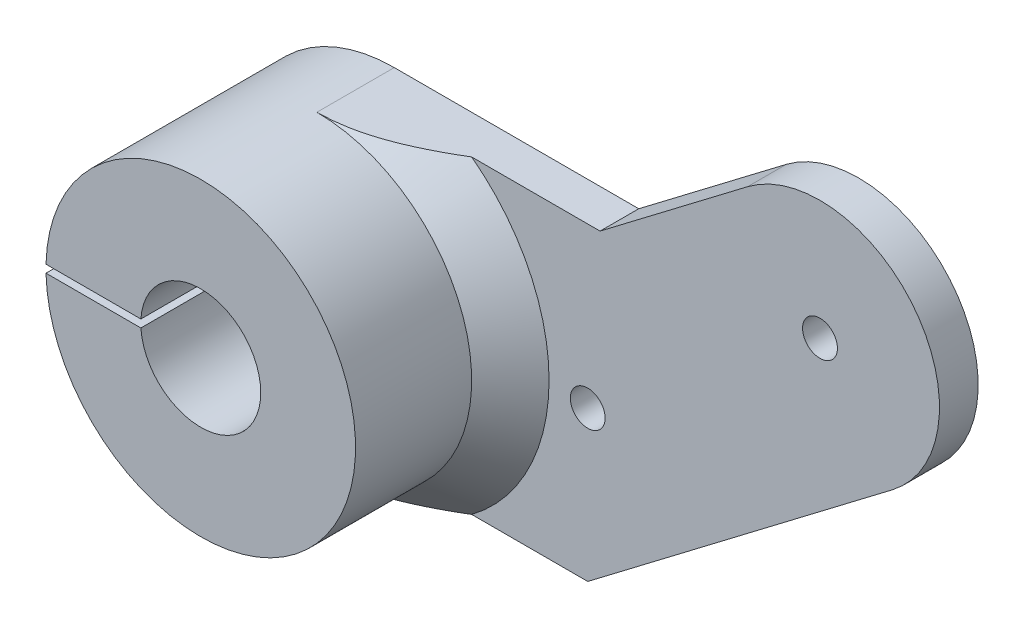
SolidWorks part; units mm, degrees
ref_plane "Front Plane" through (0, 0, 0) normal (0, 0, 1) x (1, 0, 0)
ref_plane "Top Plane" through (0, 0, 0) normal (0, 1, 0) x (1, 0, 0)
ref_plane "Right Plane" through (0, 0, 0) normal (1, 0, 0) x (0, 0, -1)
sketch "Sketch1" plane through (0, 0, 0) normal (0, 0, 1) x (1, 0, 0)
  line L0 (29.9938, -0.6088) -> (60, 22.2148) construction
  line L1 (0, 20) -> (31.5885, 20)
  line L2 (31.5885, 20) -> (50.6541, 34.5019)
  line L3 (69.3459, 9.9278) -> (30, -20)
  line L4 (30, -20) -> (0, -20)
  line L5 (-7.7339, 0.5) -> (-19.9937, 0.5)
  line L6 (-7.7339, -0.5) -> (-19.9937, -0.5)
  arc A0 (0, 20) -> (-19.9937, 0.5) centre (0, 0) ccw
  circle A1 centre (29.9938, -0.6088) radius 2.25
  circle A2 centre (60, 22.2148) radius 2.25
  arc A3 (50.6541, 34.5019) -> (69.3459, 9.9278) centre (60, 22.2148) cw
  arc A4 (-7.7339, -0.5) -> (-7.7339, 0.5) centre (0, 0) ccw
  arc A5 (-19.9937, -0.5) -> (0, -20) centre (0, 0) ccw
  circle A7 centre (60, 22.2148) radius 2 construction
  dimension "D1" = 40
  dimension "D2" = 4.5
  dimension "D5" = 15.5
  dimension "D3" = 30
  dimension "D4" = 37.7
  dimension "D6" = 0.5
  dimension "D7" = 1
extrude "Boss-Extrude1" add sketch "Sketch1" along normal blind 5
sketch "Sketch2" plane through (0, 0, 5) normal (0, 0, 1) x (1, 0, 0)
  line L6 (-7.7339, -0.5) -> (-19.9937, -0.5)
  line L7 (0, -20) -> (30, -20)
  line L8 (30, -20) -> (69.3459, 9.9278)
  line L9 (50.6541, 34.5019) -> (31.5885, 20)
  line L10 (31.5885, 20) -> (0, 20)
  line L11 (-19.9937, 0.5) -> (-7.7339, 0.5)
  line L12 (-7.7339, -0.5) -> (-19.9937, -0.5)
  line L17 (-19.9937, 0.5) -> (-7.7339, 0.5)
  arc A0 (0, -20) -> (0, 20) centre (0, 0) ccw
  arc A4 (-7.7339, -0.5) -> (-7.7339, 0.5) centre (0, 0) ccw
  arc A5 (-19.9937, -0.5) -> (0, -20) centre (0, 0) ccw
  arc A6 (69.3459, 9.9278) -> (50.6541, 34.5019) centre (60, 22.2148) ccw
  arc A7 (0, 20) -> (-19.9937, 0.5) centre (0, 0) ccw
  arc A8 (-7.7339, -0.5) -> (-7.7339, 0.5) centre (0, 0) ccw
  arc A9 (-19.9937, -0.5) -> (0, -20) centre (0, 0) ccw
  arc A11 (0, 20) -> (-19.9937, 0.5) centre (0, 0) ccw
  dimension "D1" = 0
extrude "Boss-Extrude2" add sketch "Sketch2" along normal blind 20
chamfer "Chamfer1" distance 5 angle 45 1 edges at (20, 0, 5)
